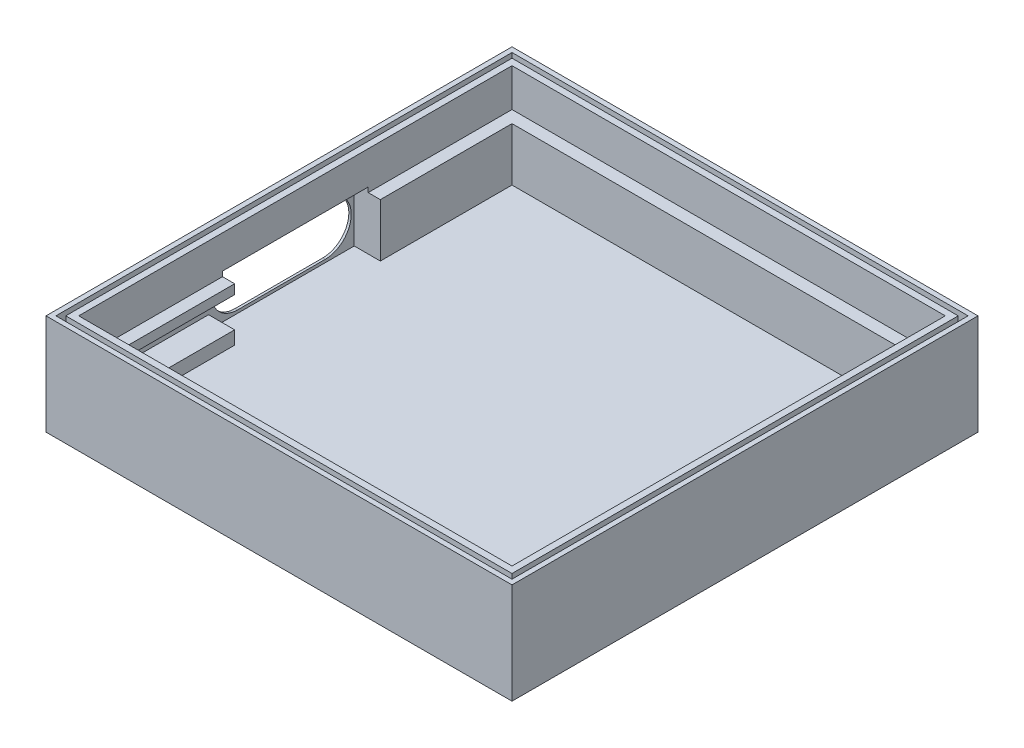
SolidWorks part; units mm, degrees
ref_plane "Front" through (0, 0, 0) normal (0, 0, 1) x (1, 0, 0)
ref_plane "Top" through (0, 0, 0) normal (0, 1, 0) x (1, 0, 0)
ref_plane "Right" through (0, 0, 0) normal (1, 0, 0) x (0, 0, -1)
sketch "Sketch2" plane through (0, 0, 0) normal (0, 1, 0) x (1, 0, 0)
  line L0 (0, -155.702) -> (0, 155.702)
  line L1 (-155.702, -155.702) -> (155.702, -155.702)
  line L2 (-155.702, -155.702) -> (-155.702, 155.702)
  line L3 (-155.702, 155.702) -> (155.702, 155.702)
  line L4 (155.702, -155.702) -> (155.702, 155.702)
  line L9 (-155.702, 0) -> (155.702, 0)
  line L11 (-152.4, 152.4) -> (152.4, 152.4)
  line L12 (-152.4, 152.4) -> (-152.4, -152.4)
  line L13 (-152.4, -152.4) -> (152.4, -152.4)
  line L14 (152.4, 152.4) -> (152.4, -152.4)
  line L15 (-152.4, 152.4) -> (152.4, -152.4) construction
  line L16 (-152.4, -152.4) -> (152.4, 152.4) construction
  line L17 (-149.098, 149.098) -> (149.098, 149.098)
  line L18 (-149.098, 149.098) -> (-149.098, -149.098)
  line L19 (-149.098, -149.098) -> (149.098, -149.098)
  line L20 (149.098, 149.098) -> (149.098, -149.098)
  line L21 (-149.098, 149.098) -> (149.098, -149.098) construction
  line L22 (-149.098, -149.098) -> (149.098, 149.098) construction
  line L23 (-144.78, 144.78) -> (144.78, 144.78)
  line L24 (-144.78, 144.78) -> (-144.78, -144.78)
  line L25 (-144.78, -144.78) -> (144.78, -144.78)
  line L26 (144.78, 144.78) -> (144.78, -144.78)
  line L27 (-144.78, 144.78) -> (144.78, -144.78) construction
  line L28 (-144.78, -144.78) -> (144.78, 144.78) construction
  line L29 (-136.652, -136.652) -> (136.652, -136.652)
  line L30 (-136.652, -136.652) -> (-136.652, 136.652)
  line L31 (-136.652, 136.652) -> (136.652, 136.652)
  line L32 (136.652, -136.652) -> (136.652, 136.652)
  line L33 (-136.652, -136.652) -> (136.652, 136.652) construction
  line L34 (-136.652, 136.652) -> (136.652, -136.652) construction
  point P8 (0, 0)
  point P13 (0, 0)
  point P18 (0, 0)
  point P25 (0, 0)
  dimension "D1" = 311.404
  dimension "D2" = 3.302
  dimension "D3" = 3.302
  dimension "D4" = 4.318
  dimension "D5" = 273.304
  dimension "D6" = 289.56
extrude "Boss-Extrude1" add sketch "Sketch2" along normal blind 67.31 contours L1 L4 L3 L2
sketch "Sketch4" plane through (0, 67.31, 0) normal (0, 1, 0) x (1, 0, 0)
  line L0 (-144.78, -144.78) -> (144.78, -144.78) construction
  line L1 (144.78, 144.78) -> (144.78, -144.78) construction
  line L2 (-144.78, 144.78) -> (144.78, 144.78) construction
  line L3 (-144.78, 144.78) -> (-144.78, -144.78) construction
  line L4 (-144.78, -144.78) -> (144.78, -144.78)
  line L5 (144.78, 144.78) -> (144.78, -144.78)
  line L6 (-144.78, 144.78) -> (144.78, 144.78)
  line L7 (-144.78, 144.78) -> (-144.78, -144.78)
extrude "Cut-Extrude1" cut sketch "Sketch4" against normal blind 25.4
sketch "Sketch5" plane through (0, 67.31, 0) normal (0, 1, 0) x (1, 0, 0)
  line L0 (-136.652, -136.652) -> (136.652, -136.652) construction
  line L1 (136.652, -136.652) -> (136.652, 136.652) construction
  line L2 (-136.652, 136.652) -> (136.652, 136.652) construction
  line L3 (-136.652, -136.652) -> (-136.652, 136.652) construction
  line L4 (-136.652, -136.652) -> (136.652, -136.652)
  line L5 (136.652, -136.652) -> (136.652, 136.652)
  line L6 (-136.652, 136.652) -> (136.652, 136.652)
  line L7 (-136.652, -136.652) -> (-136.652, 136.652)
extrude "Cut-Extrude2" cut sketch "Sketch5" against normal blind 60.96
sketch "Sketch6" plane through (0, 67.31, 0) normal (0, 1, 0) x (1, 0, 0)
  line L0 (-152.4, -152.4) -> (152.4, -152.4) construction
  line L1 (-149.098, -149.098) -> (149.098, -149.098) construction
  line L2 (152.4, 152.4) -> (152.4, -152.4) construction
  line L3 (149.098, 149.098) -> (149.098, -149.098) construction
  line L4 (-149.098, 149.098) -> (149.098, 149.098) construction
  line L5 (-152.4, 152.4) -> (152.4, 152.4) construction
  line L6 (-152.4, 152.4) -> (-152.4, -152.4) construction
  line L7 (-149.098, 149.098) -> (-149.098, -149.098) construction
  line L8 (-152.4, -152.4) -> (152.4, -152.4)
  line L9 (-149.098, -149.098) -> (149.098, -149.098)
  line L10 (152.4, 152.4) -> (152.4, -152.4)
  line L11 (149.098, 149.098) -> (149.098, -149.098)
  line L12 (-149.098, 149.098) -> (149.098, 149.098)
  line L13 (-152.4, 152.4) -> (152.4, 152.4)
  line L14 (-152.4, 152.4) -> (-152.4, -152.4)
  line L15 (-149.098, 149.098) -> (-149.098, -149.098)
extrude "Cut-Extrude3" cut sketch "Sketch6" against normal blind 12.7
sketch "Sketch7" plane through (-155.702, 0, 0) normal (-1, 0, 0) x (0, 0, 1)
  line L0 (-29.275, 25.75) -> (29.275, 25.75) construction
  line L1 (-29.275, 43.15) -> (29.275, 43.15)
  line L2 (-29.275, 8.35) -> (29.275, 8.35)
  line L3 (-46.675, 25.75) -> (46.675, 25.75) construction
  line L4 (136.652, 6.35) -> (-136.652, 6.35) construction
  arc A0 (-29.275, 43.15) -> (-29.275, 8.35) centre (-29.275, 25.75) ccw
  arc A1 (29.275, 8.35) -> (29.275, 43.15) centre (29.275, 25.75) ccw
  point P2 (0, 25.75)
  point P13 (0, 0)
  dimension "D1" = 34.8
  dimension "D2" = 93.35
  dimension "D3" = 2
extrude "Cut-Extrude4" cut sketch "Sketch7" against normal up to next
sketch "Sketch8" plane through (-136.652, 0, 0) normal (1, 0, 0) x (0, 0, -1)
  line L6 (29.275, 45.15) -> (48.675, 45.15)
  line L7 (48.675, 45.15) -> (48.675, 25.75)
  line L8 (-29.275, 6.35) -> (29.275, 6.35)
  line L9 (29.275, 45.15) -> (-29.275, 45.15)
  line L10 (-29.275, 6.35) -> (29.275, 6.35)
  line L11 (29.275, 45.15) -> (-29.275, 45.15)
  line L12 (48.675, 25.75) -> (48.675, 6.35)
  line L13 (48.675, 6.35) -> (29.275, 6.35)
  line L14 (-29.275, 45.15) -> (-48.675, 45.15)
  line L15 (-48.675, 45.15) -> (-48.675, 25.75)
  line L16 (-48.675, 25.75) -> (-48.675, 6.35)
  line L17 (-48.675, 6.35) -> (-29.275, 6.35)
  arc A9 (-29.275, 45.15) -> (-29.275, 6.35) centre (-29.275, 25.75) ccw
  arc A10 (29.275, 6.35) -> (29.275, 45.15) centre (29.275, 25.75) ccw
  arc A11 (-29.275, 45.15) -> (-29.275, 6.35) centre (-29.275, 25.75) ccw construction
  arc A12 (29.275, 6.35) -> (29.275, 45.15) centre (29.275, 25.75) ccw construction
  dimension "D1" = 2
extrude "Cut-Extrude5" cut sketch "Sketch8" against normal offset from surface (17.45 mm away) 1.6 up to face at (-155.702, 25.75, 0)
sketch "Sketch9" plane through (-155.702, 0, 0) normal (-1, 0, 0) x (0, 0, 1)
  line L5 (46.0141, 30.5) -> (48.175, 30.5)
  line L7 (46.0141, 21) -> (48.175, 21)
  line L8 (48.175, 30.5) -> (48.175, 21)
  arc A1 (29.275, 8.35) -> (29.275, 43.15) centre (29.275, 25.75) ccw construction
  arc A2 (29.275, 8.35) -> (29.275, 43.15) centre (29.275, 25.75) ccw construction
  arc A3 (46.0141, 30.5) -> (46.0141, 21) centre (29.275, 25.75) cw
  point P8 (46.675, 25.75)
  point P13 (48.175, 25.75)
  dimension "D1" = 1.5
  dimension "D2" = 9.5
extrude "Cut-Extrude6" cut sketch "Sketch9" against normal up to next
sketch "Sketch11" plane through (-136.652, 0, 0) normal (1, 0, 0) x (0, 0, -1)
  line L0 (-48.675, 41.91) -> (-48.675, 6.35) construction
  line L1 (-48.675, 35.56) -> (-124.875, 35.56)
  line L2 (-48.675, 35.56) -> (-48.675, 15.24)
  line L3 (-48.675, 15.24) -> (-124.875, 15.24)
  line L4 (-124.875, 35.56) -> (-124.875, 15.24)
  line L5 (-48.675, 41.91) -> (-144.78, 41.91) construction
  dimension "D1" = 6.35
  dimension "D2" = 76.2
  dimension "D3" = 20.32
extrude "Cut-Extrude7" cut sketch "Sketch11" against normal up to surface (17.45 mm away) up to face at (-154.102, 25.75, 0)
